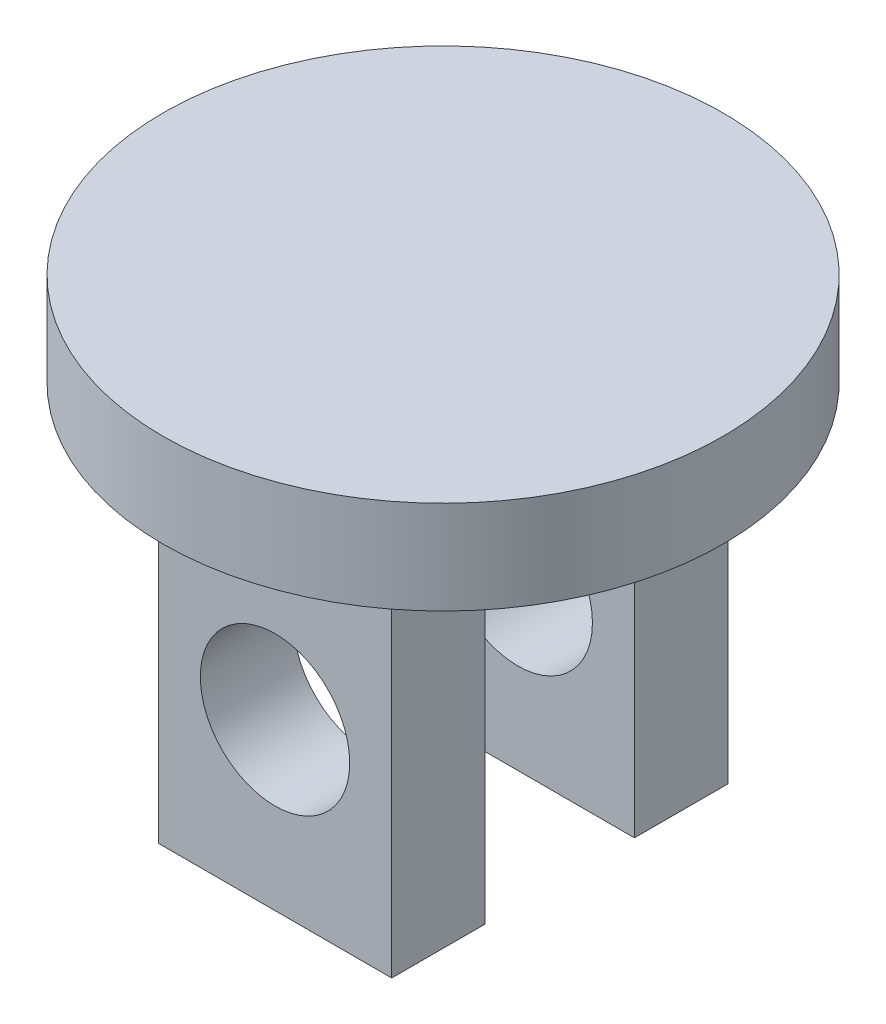
SolidWorks part; units mm, degrees
ref_plane "前视基准面" through (0, 0, 0) normal (0, 0, 1) x (1, 0, 0)
ref_plane "上视基准面" through (0, 0, 0) normal (0, 1, 0) x (1, 0, 0)
ref_plane "右视基准面" through (0, 0, 0) normal (1, 0, 0) x (0, 0, -1)
sketch "草图1" plane through (0, 0, 0) normal (0, 1, 0) x (1, 0, 0)
  line L0 (-19.4515, 0) -> (19.4515, 0) construction
  line L1 (0, 14.7897) -> (0, -14.7897) construction
  line L3 (-2.5, 3.6) -> (2.5, 3.6)
  line L4 (-2.5, 3.6) -> (-2.5, 1.6)
  line L5 (-2.5, 1.6) -> (2.5, 1.6)
  line L6 (2.5, 3.6) -> (2.5, 1.6)
  line L7 (-2.5, 3.6) -> (2.5, 1.6) construction
  line L8 (-2.5, 1.6) -> (2.5, 3.6) construction
  line L9 (-2.5, -1.6) -> (2.5, -1.6)
  line L10 (-2.5, -1.6) -> (-2.5, -3.6)
  line L11 (-2.5, -3.6) -> (2.5, -3.6)
  line L12 (2.5, -1.6) -> (2.5, -3.6)
  line L13 (-2.5, -1.6) -> (2.5, -3.6) construction
  line L14 (-2.5, -3.6) -> (2.5, -1.6) construction
  circle A0 centre (0, 0) radius 6
  point P4 (0, 0)
  point P8 (0, 0)
  point P10 (0, 2.6)
  point P15 (0, -2.6)
  dimension "D1" = 12
  dimension "D2" = 2
  dimension "D3" = 3.2
  dimension "D4" = 5
extrude "凸台-拉伸1" add sketch "草图1" along normal blind 2 contours L12 L9 L10 L11 | L6 L3 L4 L5 | A0 L9 L12 L11 L10 L3 L6 L5 L4 region at (0, 0, -2.6) region at (0, 0, 2.6) region at (0, 0, 0)
extrude "凸台-拉伸2" add sketch "草图1<3>" against normal blind 8 contours L6 L3 L4 L5 | L12 L9 L10 L11 region at (0, 0, -2.6) region at (0, 0, 2.6)
sketch "草图1<3>" plane through (0, 0, 0) normal (0, 1, 0) x (1, 0, 0) same geometry as "草图1"
sketch "草图2" plane through (0, 0, 3.6) normal (0, 0, 1) x (1, 0, 0)
  line L0 (0, 2) -> (0, -16.7904) construction
  line L1 (6, 2) -> (-6, 2) construction
  circle A0 centre (0, -4.46) radius 1.6
  dimension "D1" = 3.2
extrude "切除-拉伸1" cut sketch "草图2" against normal through all
